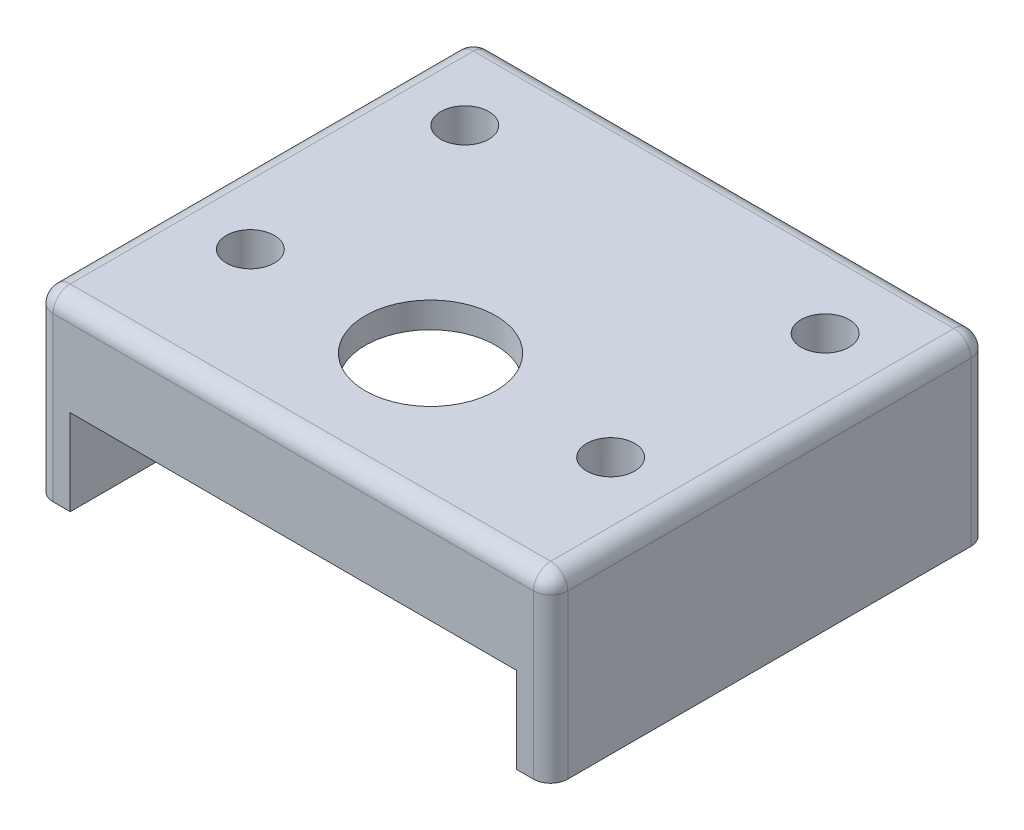
SolidWorks part; units mm, degrees
material "ABS"
ref_plane "Front Plane" through (0, 0, 0) normal (0, 0, 1) x (1, 0, 0)
ref_plane "Top Plane" through (0, 0, 0) normal (0, 1, 0) x (1, 0, 0)
ref_plane "Right Plane" through (0, 0, 0) normal (1, 0, 0) x (0, 0, -1)
sketch "Sketch1" plane through (0, 0, 0) normal (0, 1, 0) x (1, 0, 0)
  line L0 (26, 0) -> (28, 0)
  line L2 (0, 0) -> (0, 23.5)
  line L3 (0, 23.5) -> (26, 23.5)
  line L4 (26, 0) -> (26, 23.5)
  line L5 (-2, 0) -> (0, 0)
  line L6 (-2, 0) -> (-2, 25.5)
  line L7 (-2, 25.5) -> (28, 25.5)
  line L8 (28, 0) -> (28, 25.5)
  dimension "D1" = 2
  dimension "D2" = 2
  dimension "D3" = 26
  dimension "D4" = 23.5
extrude "Boss-Extrude1" add sketch "Sketch1" along normal blind 10.5
sketch "Sketch3" plane through (0, 10.5, 0) normal (0, 1, 0) x (1, 0, 0)
  line L0 (0, 0) -> (26, 0)
  line L1 (13, 26) -> (13, -49974) construction
  line L2 (2.5, 20.5) -> (23.5, 20.5) construction
  line L3 (2.5, 20.5) -> (2.5, 8) construction
  line L4 (2.5, 8) -> (23.5, 8) construction
  line L5 (23.5, 20.5) -> (23.5, 8) construction
  line L8 (-2, 0) -> (0, 0)
  line L9 (0, 0) -> (0, 23.5)
  line L10 (0, 23.5) -> (26, 23.5)
  line L11 (26, 23.5) -> (26, 0)
  line L12 (26, 0) -> (28, 0)
  line L13 (28, 0) -> (28, 25.5)
  line L14 (28, 25.5) -> (-2, 25.5)
  line L15 (-2, 25.5) -> (-2, 0)
  line L16 (-2, 0) -> (0, 0)
  line L20 (26, 0) -> (28, 0)
  line L21 (28, 0) -> (28, 25.5)
  line L22 (28, 25.5) -> (-2, 25.5)
  line L23 (-2, 25.5) -> (-2, 0)
  circle A0 centre (2.5, 20.5) radius 1.4
  circle A1 centre (2.5, 8) radius 1.4
  circle A2 centre (23.5, 8) radius 1.4
  circle A3 centre (23.5, 20.5) radius 1.4
  circle A4 centre (13, 8) radius 3.8
  point P12 (13, 20.5)
  point P19 (13, 25.5)
  dimension "D4" = 7.6
  dimension "D5" = 2.8
  dimension "D2" = 21
  dimension "D3" = 12.5
  dimension "D6" = 5
  dimension "D1" = 0
extrude "Boss-Extrude2" add sketch "Sketch3" against normal blind 1.5
sketch "Sketch4" plane through (0, 9, 0) normal (0, -1, 0) x (1, 0, 0)
  line L0 (0, 0) -> (26, 0) construction
  line L1 (0, 0) -> (26, 0)
  line L2 (0, 0) -> (0, -2)
  line L3 (0, -2) -> (26, -2)
  line L4 (26, 0) -> (26, -2)
  line L6 (26, -23.5) -> (26, 0) construction
  line L7 (0, 0) -> (0, -23.5) construction
  line L12 (2.5, -5.5) -> (0, -5.5)
  line L13 (0, -5.5) -> (0, -10.5)
  line L14 (0, -10.5) -> (2.5, -10.5)
  line L15 (2.5, -5.5) -> (2.5, -10.5) construction
  line L16 (13, 0) -> (13, -50000) construction
  line L17 (13, -14.25) -> (17.2847, -14.25) construction
  line L18 (2.5, -23) -> (0, -23)
  line L19 (0, -23) -> (0, -18)
  line L20 (0, -18) -> (2.5, -18)
  line L21 (26, -23) -> (26, -18)
  line L22 (23.5, -23) -> (26, -23)
  line L23 (26, -18) -> (23.5, -18)
  line L24 (23.5, -5.5) -> (26, -5.5)
  line L25 (26, -5.5) -> (26, -10.5)
  line L26 (26, -10.5) -> (23.5, -10.5)
  circle A0 centre (23.5, -8) radius 1.4 construction
  circle A1 centre (23.5, -20.5) radius 1.4 construction
  circle A2 centre (2.5, -20.5) radius 1.4 construction
  circle A3 centre (2.5, -8) radius 1.4 construction
  circle A4 centre (23.5, -8) radius 1.4
  circle A5 centre (23.5, -20.5) radius 1.4
  circle A6 centre (2.5, -20.5) radius 1.4
  circle A7 centre (2.5, -8) radius 1.4
  arc A8 (2.5, -5.5) -> (2.5, -10.5) centre (2.5, -8) cw
  arc A9 (2.5, -23) -> (2.5, -18) centre (2.5, -20.5) ccw
  arc A10 (23.5, -23) -> (23.5, -18) centre (23.5, -20.5) cw
  arc A11 (23.5, -5.5) -> (23.5, -10.5) centre (23.5, -8) ccw
  point P28 (13, 0)
  dimension "D1" = 2
  dimension "D2" = 5
extrude "Boss-Extrude3" add sketch "Sketch4" along normal blind 4
fillet "Fillet1" radius 1 16 edges at (28, 5.25, 0) (-2, 5.25, 0) (13, 10.5, -25.5) (13, 9, -23.5) (13, 9, -2) (26, 9, -3.75) (26, 9, -14.25) (0, 9, -3.75) (0, 9, -14.25) (0, 4.5, -23.5) (28, 5.25, -25.5) (26, 4.5, -23.5) (-2, 5.25, -25.5) (-2, 10.5, -12.75) (13, 10.5, 0) (28, 10.5, -12.75)
